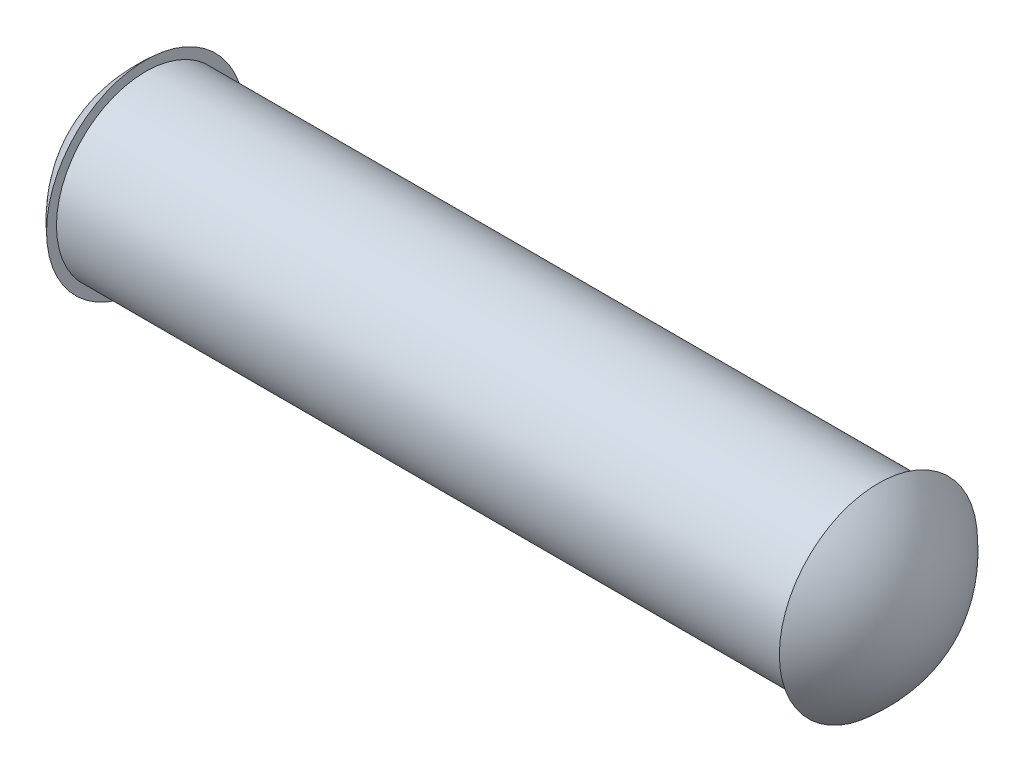
SolidWorks part; units mm, degrees
material "Cast Alloy Steel"
ref_plane "Front Plane" through (0, 0, 0) normal (0, 0, 1) x (1, 0, 0)
ref_plane "Top Plane" through (0, 0, 0) normal (0, 1, 0) x (1, 0, 0)
ref_plane "Right Plane" through (0, 0, 0) normal (1, 0, 0) x (0, 0, -1)
sketch "Sketch1" plane through (0, 0, 0) normal (1, 0, 0) x (0, 0, -1)
  circle A0 centre (0, 0) radius 2.286
  dimension "D1" = 4.572
extrude "Boss-Extrude1" add sketch "Sketch1" along normal blind 9.398 and the other way blind 9.398
sketch "Sketch5" plane through (0, 0, 0) normal (0, 1, 0) x (1, 0, 0)
  line L0 (9.398, 0) -> (9.398, 2.54)
  line L1 (9.398, -2.286) -> (9.398, 2.286) construction
  line L2 (9.398, 0) -> (10.668, 0)
  line L3 (10.668, 0) -> (10.668, -2.1779) construction
  line L4 (9.398, 2.54) -> (7.9267, 2.54) construction
  spline S0 degree 2 poles (9.398, 2.54) (10.668, 1.4199) (10.668, 0) knots 0 0 0 1 1 1
  dimension "D1" = 2.54
  dimension "D2" = 1.27
revolve "Revolve1" add sketch "Sketch5" angle 360 about L2
mirror "Mirror1" about plane through (0, 0, 0) normal (1, 0, 0) of "Revolve1"
